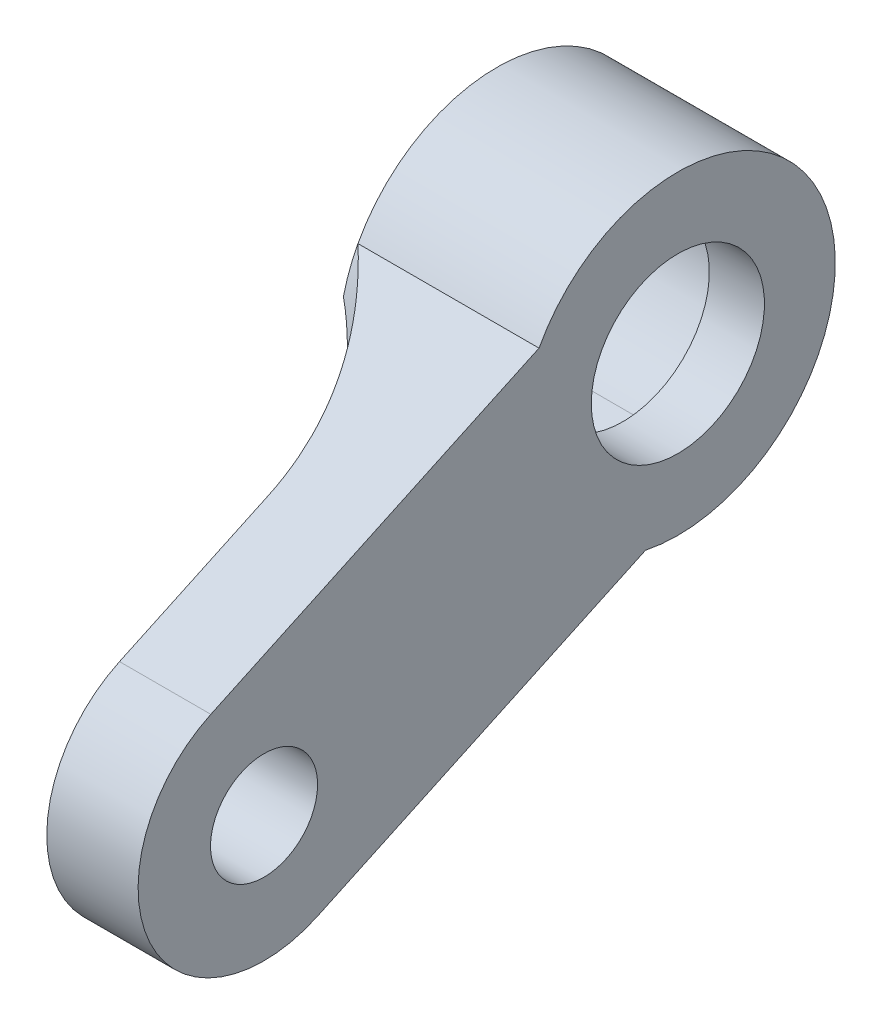
SolidWorks part; units mm, degrees
ref_plane "Front Plane" through (0, 0, 0) normal (0, 0, 1) x (1, 0, 0)
ref_plane "Top Plane" through (0, 0, 0) normal (0, 1, 0) x (1, 0, 0)
ref_plane "Right Plane" through (0, 0, 0) normal (1, 0, 0) x (0, 0, -1)
ref_plane "Plane1" through (41.15, 0, 0) normal (-1, 0, 0) x (0, -1, 0)
sketch "Sketch1" plane through (41.15, 0, 0) normal (-1, 0, 0) x (0, -1, 0)
  circle A2 centre (19.3633, -42.4025) radius 5
  dimension "D1" = 10
extrude "Boss-Extrude1" add sketch "Sketch1" against normal blind 2.85
draft "Draft1" [suppressed] type of draft neutral plane draft angle 45 faces to draft 1 reverse direction yes parameters "D1"=45
sketch "Sketch2" plane through (44, 0, 0) normal (1, 0, 0) x (0, 0, -1)
  line L0 (44.093, -22.9885) -> (30.9515, -29.1165)
  line L1 (27.5706, -21.866) -> (40.712, -15.738)
  arc A0 (30.9515, -29.1165) -> (27.5706, -21.866) centre (29.261, -25.4912) cw
  arc A1 (40.712, -15.738) -> (44.093, -22.9885) centre (42.4025, -19.3633) cw
  circle A2 centre (42.4025, -19.3633) radius 5 construction
extrude "Boss-Extrude2" add sketch "Sketch2" along normal blind 2.9
extrude "Boss-Extrude3" add sketch "Sketch1<2>" against normal up to surface (5.75 mm away) up to face at (46.9, -22.4272, -35.8318)
sketch "Sketch1<2>" plane through (41.15, 0, 0) normal (-1, 0, 0) x (0, -1, 0) same geometry as "Sketch1"
hole_wizard "Hole1" positions "Sketch4" profile "Sketch3" legacy end condition through all
sketch "Sketch4" plane through (46.9, 0, 0) normal (1, 0, 0) x (0, 0, -1)
  arc A2 (27.5706, -21.866) -> (30.9515, -29.1165) centre (29.261, -25.4912) ccw construction
  point P0 (29.261, -25.4912)
sketch "Sketch3" plane through (46.9, -25.4912, -29.261) normal (0, 1, 0) x (0, 0, -1)
  line L0 (0, 0) -> (0, 5.75)
  line L1 (0, 5.75) -> (1.7, 5.75)
  line L2 (1.7, 5.75) -> (1.7, 0)
  line L3 (1.7, 0) -> (0, 0)
  line L4 (0, 110) -> (0, -10) construction
  dimension "Diameter" = 3.4
  dimension "Depth" = 5.75
hole_wizard "Hole2" positions "Sketch6" profile "Sketch5" legacy end condition through all
sketch "Sketch6" plane through (41.15, 0, 0) normal (-1, 0, 0) x (0, 0, 1)
  circle A0 centre (-42.4025, -19.3633) radius 5 construction
  point P0 (-42.4025, -19.3633)
sketch "Sketch5" plane through (41.15, -19.3633, -42.4025) normal (0, 1, 0) x (0, 0, 1)
  line L0 (0, 0) -> (0, 5.75)
  line L1 (0, 5.75) -> (2.75, 5.75)
  line L2 (2.75, 5.75) -> (2.75, 2.8)
  line L3 (2.75, 2.8) -> (2.2, 2.8)
  line L4 (2.2, 2.8) -> (2.2, 0)
  line L5 (2.2, 0) -> (0, 0)
  line L6 (0, 110) -> (0, -10) construction
  dimension "Diameter" = 5.5
  dimension "Depth" = 5.75
  dimension "C-Bore Diameter" = 4.4
  dimension "C-Bore Depth" = 2.8
chamfer "Chamfer1" distance 0.5 angle 45 1 edges at (41.15, -19.3633, -40.2025)
fillet "Fillet1" radius 6 1 edges at (44, -21.4764, -37.871) tangent propagation no
sketch "Sketch7" plane through (41.15, 0, 0) normal (-1, 0, 0) x (0, 0, 1)
  line L0 (-42.4025, -19.3633) -> (-29.261, -25.4912) construction
  line L1 (-40.4423, -16.3437) -> (-33.4127, -20.9072)
  line L2 (-33.4127, -20.9072) -> (-35.4413, -25.2574)
  line L3 (-35.4413, -25.2574) -> (-43.4556, -22.8058)
  arc A0 (-40.4423, -16.3437) -> (-43.4556, -22.8058) centre (-42.4025, -19.3633) ccw
  point P7 (-34.427, -23.0823)
  dimension "D1" = 7.2
  dimension "D2" = 4.8
  dimension "D3" = 8.8
extrude "Cut-Extrude1" cut sketch "Sketch7" against normal blind 4
